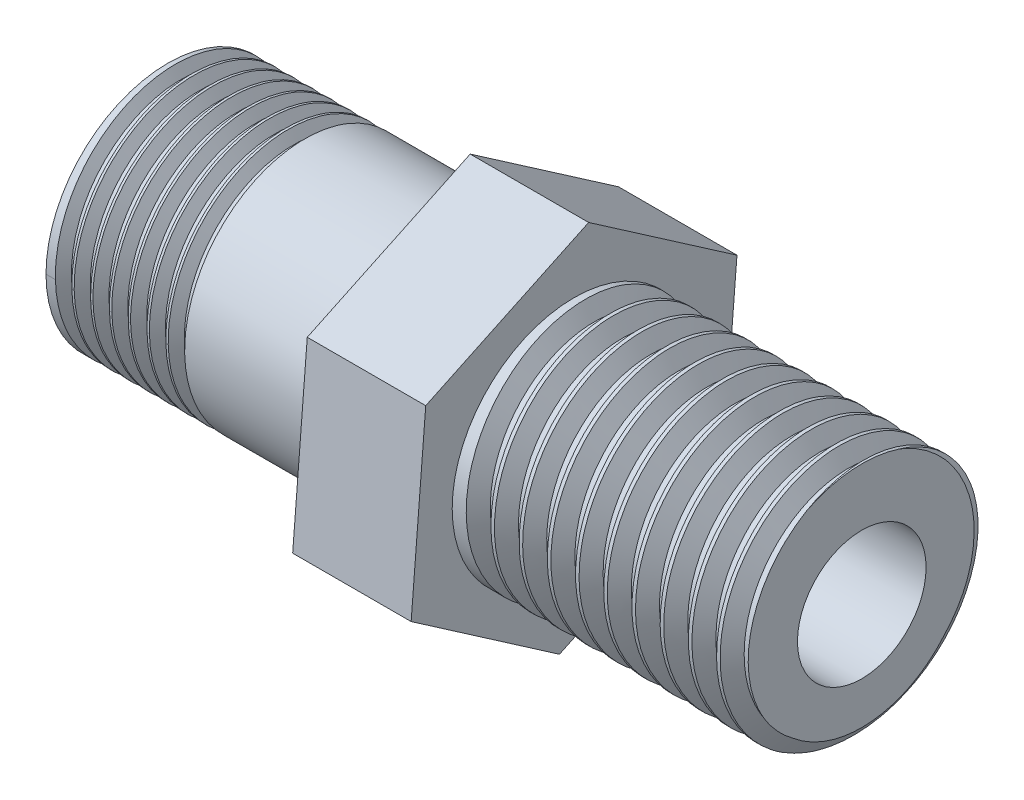
SolidWorks part; units mm, degrees
material "6061 Alloy"
ref_plane "Front Plane" through (0, 0, 0) normal (0, 0, 1) x (1, 0, 0)
ref_plane "Top Plane" through (0, 0, 0) normal (0, 1, 0) x (1, 0, 0)
ref_plane "Right Plane" through (0, 0, 0) normal (1, 0, 0) x (0, 0, -1)
sketch "Sketch1" plane through (0, 0, 0) normal (1, 0, 0) x (0, 0, -1)
  circle A0 centre (0, 0) radius 4.826
  circle A1 centre (0, 0) radius 9.144
extrude "Boss-Extrude1" add sketch "Sketch1" along normal blind 21.59 contours A0 | A1
thread "Thread1" pitch 2.1167 method cut profile "Thread Profile1" start angle 0, offset 0, length 0, pitch 2.1167, diameter 18.288
ref_plane "Plane1" through (0, 0, -9.144) normal (0, -1, 0) x (0, 0, -1)
sketch "Thread Profile1" plane through (0, 0, -9.144) normal (0, -1, 0) x (0, 0, -1)
  line L0 (0, 0) -> (0, 2.1167) construction
  line L11 (0, 0) -> (0, 1.8521)
  line L12 (0, 1.8521) -> (-1.1457, 1.1906)
  line L13 (-1.1457, 1.1906) -> (-1.1457, 0.6615)
  line L15 (-1.1457, 0.6615) -> (0, 0)
  line L17 (-1.1457, 0.926) -> (0, 0.926) construction
  point P2 (0, 0)
  dimension "Pitch" = 2.1167
  dimension "Profile_Angle" = 60
  dimension "Profile_Land" = 0.5292
  dimension "Profile_Height" = 1.1457
sketch "Sketch5" plane through (0, 0, 0) normal (-1, 0, 0) x (0, 0, 1)
  line L1 (-11.1297, -7.6902) -> (1.095, -13.4837)
  line L2 (1.095, -13.4837) -> (12.2248, -5.7935)
  line L3 (12.2248, -5.7935) -> (11.1297, 7.6902)
  line L4 (11.1297, 7.6902) -> (-1.095, 13.4837)
  line L5 (-1.095, 13.4837) -> (-12.2248, 5.7935)
  line L6 (-12.2248, 5.7935) -> (-11.1297, -7.6902)
  circle A0 centre (0, 0) radius 4.826
  circle A1 centre (0, 0) radius 11.7157 construction
extrude "Boss-Extrude2" add sketch "Sketch5" along normal blind 30.48
sketch "Sketch6" plane through (-30.48, 0, 0) normal (-1, 0, 0) x (0, 0, 1)
  circle A0 centre (0, 0) radius 4.826
  circle A1 centre (0, 0) radius 7.644
extrude "Boss-Extrude3" [suppressed] add sketch "Sketch6" along normal blind 97.79
sketch "Sketch7" plane through (0, 0, 0) normal (0, 0, 1) x (1, 0, 0)
  spline S0 degree 3 poles (-130.6648, 16.9185) (-90.6933, 17.2365) (-106.8117, 4.2187) (-98.2788, -3.7063) (-104.7173, -22.378) (-124.7095, -8.6619) (-130.6648, 16.9185) (-90.6933, 17.2365) (-106.8117, 4.2187) knots -0.670234 -0.466566 -0.255088 0 0.103666 0.168758 0.329766 0.533434 0.744912 1 1.103666 1.168758 1.329766 only from (-99.6907, 11.6491) to (-99.6907, 11.6491)
extrude "Cut-Extrude1" [suppressed] cut sketch "Sketch7" against normal blind 97.79 and the other way blind 97.79
sketch "Sketch8" plane through (-30.48, 0, 0) normal (-1, 0, 0) x (0, 0, 1)
  circle A0 centre (0, 0) radius 6.35
extrude "Cut-Extrude2" cut sketch "Sketch8" against normal blind 15.24
chamfer "Chamfer1" distance 1.524 angle 45 1 edges at (-30.48, 0, 6.35)
sketch "Sketch9" plane through (-30.48, 0, 0) normal (-1, 0, 0) x (0, 0, 1)
  circle A0 centre (0, 0) radius 9.144
  circle A1 centre (0, 0) radius 17.8055
extrude "Cut-Extrude3" cut sketch "Sketch9" against normal blind 21.59
thread "Thread2" pitch 1.4111 method cut profile "Thread Profile2" start angle 0, offset 0, length 10, pitch 1.4111, diameter 18.288
ref_plane "Plane2" through (-30.48, 0, -9.144) normal (0, -1, 0) x (0, 0, -1)
sketch "Thread Profile2" plane through (-30.48, 0, -9.144) normal (0, -1, 0) x (0, 0, -1)
  line L0 (0, 0) -> (0, 1.4111) construction
  line L11 (0, 0) -> (0, 1.2347)
  line L12 (0, 1.2347) -> (-0.7638, 0.7937)
  line L13 (-0.7638, 0.7937) -> (-0.7638, 0.441)
  line L15 (-0.7638, 0.441) -> (0, 0)
  line L17 (-0.7638, 0.6174) -> (0, 0.6174) construction
  point P2 (0, 0)
  dimension "Pitch" = 1.4111
  dimension "Profile_Angle" = 60
  dimension "Profile_Land" = 0.3528
  dimension "Profile_Height" = 0.7638
